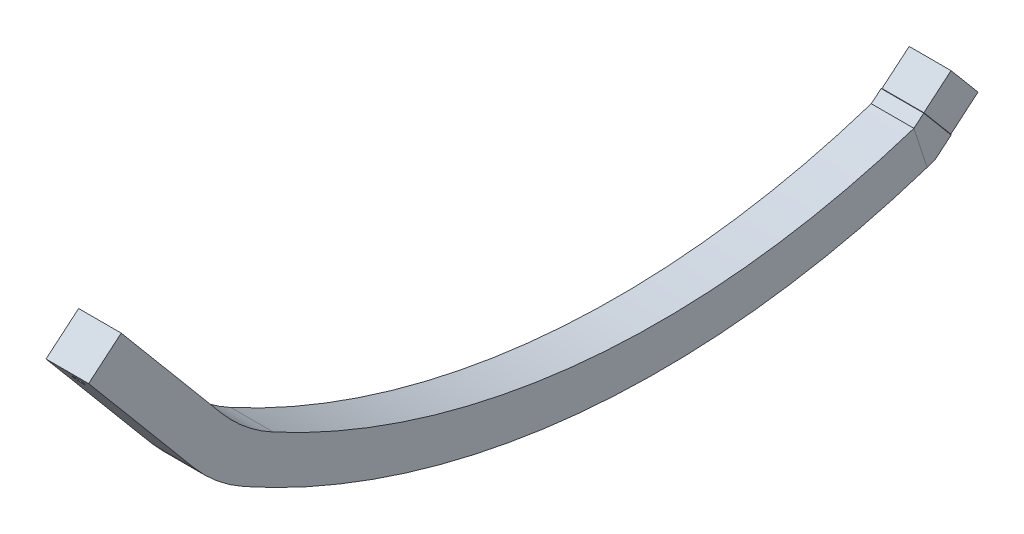
SolidWorks part; units mm, degrees
ref_plane "Ebene vorne" through (0, 0, 0) normal (0, 0, 1) x (1, 0, 0)
ref_plane "Ebene oben" through (0, 0, 0) normal (0, 1, 0) x (1, 0, 0)
ref_plane "Ebene rechts" through (0, 0, 0) normal (1, 0, 0) x (0, 0, -1)
sketch "Skizze1" plane through (0, 0, 0) normal (1, 0, 0) x (0, 0, -1)
  line L0 (0, 12) -> (-233.4212, 12) construction
  line L1 (-240, 65) -> (-230.7357, 72.7737)
  line L2 (0, 12) -> (-3.7358, 23.4037)
  line L3 (0, 12) -> (0, 39.1297) construction
  line L4 (0, 0) -> (-218.6687, 0) construction
  arc A0 (0, 12) -> (-240, 65) centre (-75.176, 241.4765) cw
  arc A1 (-3.7358, 23.4037) -> (-230.7357, 72.7737) centre (-75.176, 241.4765) cw
  dimension "D1" = 53
  dimension "D2" = 240
  dimension "D3" = 40
  dimension "D4" = 12
  dimension "D5" = 12
extrude "Aufsatz-Linear austragen1" add sketch "Skizze1" along normal blind 12
sketch "Skizze4" plane through (0, 0, 0) normal (1, 0, 0) x (0, 0, -1)
  line L0 (-230.7357, 72.7737) -> (-240, 65) construction
  line L2 (-3.7358, 23.4037) -> (6.769, 32.2183)
  line L3 (6.769, 32.2183) -> (14.4825, 23.0258)
  line L4 (14.4825, 23.0258) -> (2.2258, 12.7411)
  line L5 (-3.7358, 23.4037) -> (0, 12)
  arc A0 (0, 12) -> (2.2258, 12.7411) centre (-75.176, 241.4765) ccw
  arc A4 (-240, 65) -> (0, 12) centre (-75.176, 241.4765) ccw construction
  dimension "D1" = 16
  dimension "D2" = 12
extrude "Aufsatz-Linear austragen3" add sketch "Skizze4" along normal blind 12 separate body
sketch "Skizze5" plane through (12, 0, 0) normal (1, 0, 0) x (0, 0, -1)
  line L0 (-231.6625, 71.996) -> (-222.47, 79.7094)
  line L1 (-230.7357, 72.7737) -> (-232.109, 74.04) construction
  line L2 (-231.6625, 71.996) -> (-220.0923, 58.2072)
  line L3 (-230.7357, 72.7737) -> (-240, 65) construction
  line L4 (-222.47, 79.7094) -> (-210.8998, 65.9206)
  line L5 (-220.0923, 58.2072) -> (-192.9483, 44.5269)
  line L6 (-220.0923, 58.2072) -> (-211.3409, 65.5505) construction
  line L7 (-210.8998, 65.9206) -> (-192.9483, 44.5269)
  arc A6 (-230.7357, 72.7737) -> (-3.7358, 23.4037) centre (-75.176, 241.4765) ccw construction
  dimension "D1" = 12
  dimension "D2" = 1.2
  dimension "D3" = 18
extrude "Aufsatz-Linear austragen4" add sketch "Skizze5" against normal up to surface (12 mm away) up to face at (0, 27.378, 122.107)
sketch "Skizze6" plane through (12, 0, 0) normal (1, 0, 0) x (0, 0, -1)
  line L0 (-231.6625, 71.996) -> (-199.5106, 33.6789)
  line L1 (-199.5106, 33.6789) -> (-204.3677, 29.6033)
  line L2 (-204.3677, 29.6033) -> (-240, 65)
  line L3 (-240, 65) -> (-231.6625, 71.996)
extrude "Schnitt-Linear austragen1" cut sketch "Skizze6" against normal through all
sketch "Skizze7" plane through (12, 0, 0) normal (1, 0, 0) x (0, 0, -1)
  line L0 (-222.47, 79.7094) -> (-229.5406, 88.1359)
  line L1 (-192.9483, 44.5269) -> (-222.47, 79.7094) construction
  line L2 (-229.5406, 88.1359) -> (-238.7332, 80.4225)
  line L3 (-238.7332, 80.4225) -> (-231.6625, 71.996)
  line M4 (-222.47, 79.7094) -> (-231.6625, 71.996)
  dimension "D1" = 11
extrude "Aufsatz-Linear austragen5" [suppressed] add sketch "Skizze7" against normal up to surface (12 mm away) contours L2 L3 L0 M4
fillet "Verrundung1" radius 50 2 edges at (6, 35.2854, 200.8587) (6, 44.5269, 192.9483)
sketch "Skizze8" [suppressed] plane through (0, -76.6111, 91.3015) normal (0, 0.6428, -0.766) x (-1, 0, 0)
  line L0 (-6, 215.0619) -> (-6, 184.7045) construction
  line L1 (0, 215.0619) -> (-12, 215.0619) construction
  circle A0 centre (-6, 210.0619) radius 1.55
  dimension "D2" = 3.1
  dimension "D1" = 5
extrude "Schnitt-Linear austragen2" [suppressed] cut sketch "Skizze8" against normal blind 6
sketch "Skizze9" plane through (0, 156.3205, 131.1685) normal (0, 0.766, 0.6428) x (1, 0, 0)
  line L0 (6, -119.1857) -> (6, -131.1857) construction
  line L1 (0, -119.1857) -> (12, -119.1857) construction
  line L2 (0, -131.1857) -> (12, -131.1857) construction
  line L3 (12, -125.1857) -> (0, -125.1857) construction
  line L4 (12, -119.1857) -> (12, -131.1857) construction
  line L5 (0, -119.1857) -> (0, -131.1857) construction
  line L7 (0, -131.1857) -> (12, -131.1857)
  line L8 (0, -131.1857) -> (0, -119.1857)
  line L9 (0, -119.1857) -> (12, -119.1857)
  line L10 (12, -131.1857) -> (12, -119.1857)
  line L11 (0, -131.1857) -> (12, -119.1857) construction
  line L12 (0, -119.1857) -> (12, -131.1857) construction
  point P12 (6, -125.1857)
  dimension "D1" = 12
extrude "Aufsatz-Linear austragen6" add sketch "Skizze9" along normal blind 7
sketch "Skizze10" plane through (0, 16.6449, -19.8366) normal (0, 0.6428, -0.766) x (-1, 0, 0)
  line L0 (-6, 20.3296) -> (-6, 8.3296) construction
  line L1 (-12, 20.3296) -> (0, 20.3296) construction
  line L2 (-12, 8.3296) -> (0, 8.3296) construction
  line L4 (-11.9, 8.4296) -> (-0.1, 8.4296)
  line L5 (-11.9, 8.4296) -> (-11.9, 20.2296)
  line L6 (-11.9, 20.2296) -> (-0.1, 20.2296)
  line L7 (-0.1, 8.4296) -> (-0.1, 20.2296)
  line L8 (-11.9, 8.4296) -> (-0.1, 20.2296) construction
  line L9 (-11.9, 20.2296) -> (-0.1, 8.4296) construction
  circle A0 centre (-6, 14.3296) radius 9.0363
  point P6 (-6, 14.3296)
  dimension "D1" = 11.8
extrude "Schnitt-Linear austragen3" cut sketch "Skizze10" against normal blind 10
sketch "Skizze11" plane through (0, -76.6111, 91.3015) normal (0, 0.6428, -0.766) x (-1, 0, 0)
  line L0 (-6, 211.0619) -> (-6, 204.6824) construction
  line L1 (-12, 211.0619) -> (0, 211.0619) construction
  circle A0 centre (-6, 206.0619) radius 1.55
  dimension "D1" = 3.1
  dimension "D2" = 5
extrude "Schnitt-Linear austragen4" cut sketch "Skizze11" against normal through all
chamfer "Fase1" distance 0.1 angle 45 4 edges at (0, 21.1941, -2.9653) (6, 16.5979, -6.822) (12, 21.1941, -2.9653) (6, 25.7904, 0.8914)
